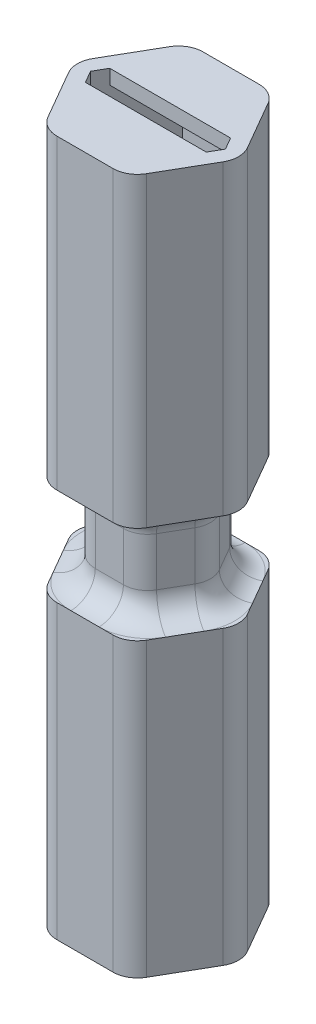
SolidWorks part; units mm, degrees
ref_plane "Front Plane" through (0, 0, 0) normal (0, 0, 1) x (1, 0, 0)
ref_plane "Top Plane" through (0, 0, 0) normal (0, 1, 0) x (1, 0, 0)
ref_plane "Right Plane" through (0, 0, 0) normal (1, 0, 0) x (0, 0, -1)
sketch "Sketch1" plane through (0, 0, 0) normal (0, 1, 0) x (1, 0, 0)
  line L1 (17.3205, 0) -> (8.6603, 15)
  line L2 (8.6603, 15) -> (-8.6603, 15)
  line L3 (-8.6603, 15) -> (-17.3205, 0)
  line L4 (-17.3205, 0) -> (-8.6603, -15)
  line L5 (-8.6603, -15) -> (8.6603, -15)
  line L6 (8.6603, -15) -> (17.3205, 0)
  line L7 (13.8564, 0) -> (6.9282, 12)
  line L8 (6.9282, 12) -> (-6.9282, 12)
  line L9 (-6.9282, 12) -> (-13.8564, 0)
  line L10 (-13.8564, 0) -> (-6.9282, -12)
  line L11 (-6.9282, -12) -> (6.9282, -12)
  line L12 (6.9282, -12) -> (13.8564, 0)
  line L13 (11.547, 0) -> (5.7735, 10)
  line L14 (5.7735, 10) -> (-5.7735, 10)
  line L15 (-5.7735, 10) -> (-11.547, 0)
  line L16 (-11.547, 0) -> (-5.7735, -10)
  line L17 (-5.7735, -10) -> (5.7735, -10)
  line L18 (5.7735, -10) -> (11.547, 0)
  line L19 (4.0415, -7) -> (8.0829, 0)
  line L20 (8.0829, 0) -> (4.0415, 7)
  line L21 (4.0415, 7) -> (-4.0415, 7)
  line L22 (-4.0415, 7) -> (-8.0829, 0)
  line L23 (-8.0829, 0) -> (-4.0415, -7)
  line L24 (-4.0415, -7) -> (4.0415, -7)
  circle A0 centre (0, 0) radius 15 construction
  circle A1 centre (0, 0) radius 12 construction
  circle A2 centre (0, 0) radius 10 construction
  circle A3 centre (0, 0) radius 7 construction
  point P1 (4.5968, -4.245)
  dimension "D1" = 30
  dimension "D2" = 3
  dimension "D3" = 20
  dimension "D4" = 3
extrude "Boss-Extrude1" add sketch "Sketch1" along normal blind 10 contours L17 L18 L13 L14 L15 L16 L24 L23 L22 L21 L20 L19 region at (8.3957, 0, 4.8472)
extrude "Boss-Extrude2" add sketch "Sketch1<3>" against normal blind 5 contours L11 L12 L7 L8 L9 L10 L18 L17 L16 L15 L14 L13 | L17 L18 L13 L14 L15 L16 L24 L23 L22 L21 L20 L19 region at (10.0748, 0, 5.8167) region at (8.3957, 0, 4.8472)
sketch "Sketch1<3>" plane through (0, 0, 0) normal (0, 1, 0) x (1, 0, 0) same geometry as "Sketch1"
extrude "Boss-Extrude3" add sketch "Sketch1<4>" against normal blind 60 contours L5 L6 L1 L2 L3 L4 L12 L11 L10 L9 L8 L7 region at (12.5935, 0, 7.2709)
sketch "Sketch1<4>" plane through (0, 0, 0) normal (0, 1, 0) x (1, 0, 0) same geometry as "Sketch1"
fillet "Fillet1" radius 5 6 edges at (-8.6603, -30, -15) (-17.3205, -30, 0) (-8.6603, -30, 15) (8.6603, -30, 15) (17.3205, -30, 0) (8.6603, -30, -15)
mirror "Mirror1" about plane through (0, 10, 0) normal (0, 1, 0) of "Fillet1", "Boss-Extrude2", "Boss-Extrude3", "Boss-Extrude1"
sketch "Sketch2" plane through (0, 80, 0) normal (0, 1, 0) x (1, 0, 0)
  line L0 (-15.8771, 2.5) -> (15.8771, 2.5)
  line L1 (17.3205, 0) -> (8.6603, 15)
  line L2 (8.6603, 15) -> (-8.6603, 15)
  line L3 (-8.6603, 15) -> (-17.3205, 0)
  line L4 (-17.3205, 0) -> (-8.6603, -15)
  line L5 (-8.6603, -15) -> (8.6603, -15)
  line L6 (8.6603, -15) -> (17.3205, 0)
  line L8 (15.8771, -2.5) -> (-15.8771, -2.5)
  circle A0 centre (0, 0) radius 15 construction
  point P13 (8.8776, -15.3765)
  line M9 (13.8564, 0) -> (6.9282, -12)
  line M10 (6.9282, -12) -> (-6.9282, -12)
  line M11 (-6.9282, -12) -> (-13.8564, 0)
  line M12 (-13.8564, 0) -> (-6.9282, 12)
  line M13 (-6.9282, 12) -> (6.9282, 12)
  line M14 (6.9282, 12) -> (13.8564, 0)
  line M15 (-5.7735, -15) -> (5.7735, -15)
  line M16 (10.1036, -12.5) -> (15.8771, -2.5)
  line M17 (15.8771, 2.5) -> (10.1036, 12.5)
  line M18 (5.7735, 15) -> (-5.7735, 15)
  line M19 (-10.1036, 12.5) -> (-15.8771, 2.5)
  line M20 (-15.8771, -2.5) -> (-10.1036, -12.5)
  arc M23 (-5.7735, 15) -> (-10.1036, 12.5) centre (-5.7735, 10) ccw
  arc M24 (-15.8771, 2.5) -> (-15.8771, -2.5) centre (-11.547, 0) ccw
  arc M25 (-10.1036, -12.5) -> (-5.7735, -15) centre (-5.7735, -10) ccw
  arc M26 (5.7735, -15) -> (10.1036, -12.5) centre (5.7735, -10) ccw
  arc M27 (15.8771, -2.5) -> (15.8771, 2.5) centre (11.547, 0) ccw
  arc M28 (10.1036, 12.5) -> (5.7735, 15) centre (5.7735, 10) ccw
  dimension "D2" = 30
  dimension "D1" = 5
extrude "Boss-Extrude4" add sketch "Sketch2" along normal blind 3 contours M28 M18 M23 M19 M24 M20 M25 M15 M26 M16 M27 M17 M14 M9 M10 M11 M12 M13 | L0 M12 M14 M13 | L8 M9 M11 M10 | L8 M16 M9 M10 M11 M20 M25 M15 M26 | L8 L0 M27 M14 M9 | L8 L0 M11 M12 M24 region at (-12.6948, 80, -7.3294) region at (-14.7113, 80, 0) region at (0, 80, -6.801) region at (-14.1451, 80, 2.8413) region at (14.7113, 80, 0) region at (0, 80, 6.801)
fillet "Fillet2" radius 5 18 edges at (-8.6603, 20, -5) (0, 20, -10) (8.6603, 20, -5) (8.6603, 20, 5) (0, 20, 10) (-8.6603, 20, 5) (8.6603, 0, 5) (8.6603, 0, -5) (0, 0, -10) (-8.6603, 0, -5) (-8.6603, 0, 5) (0, 0, 10) (5.7735, 10, 10) (-5.7735, 10, 10) (-11.547, 10, 0) (-5.7735, 10, -10) (11.547, 10, 0) (5.7735, 10, -10)
